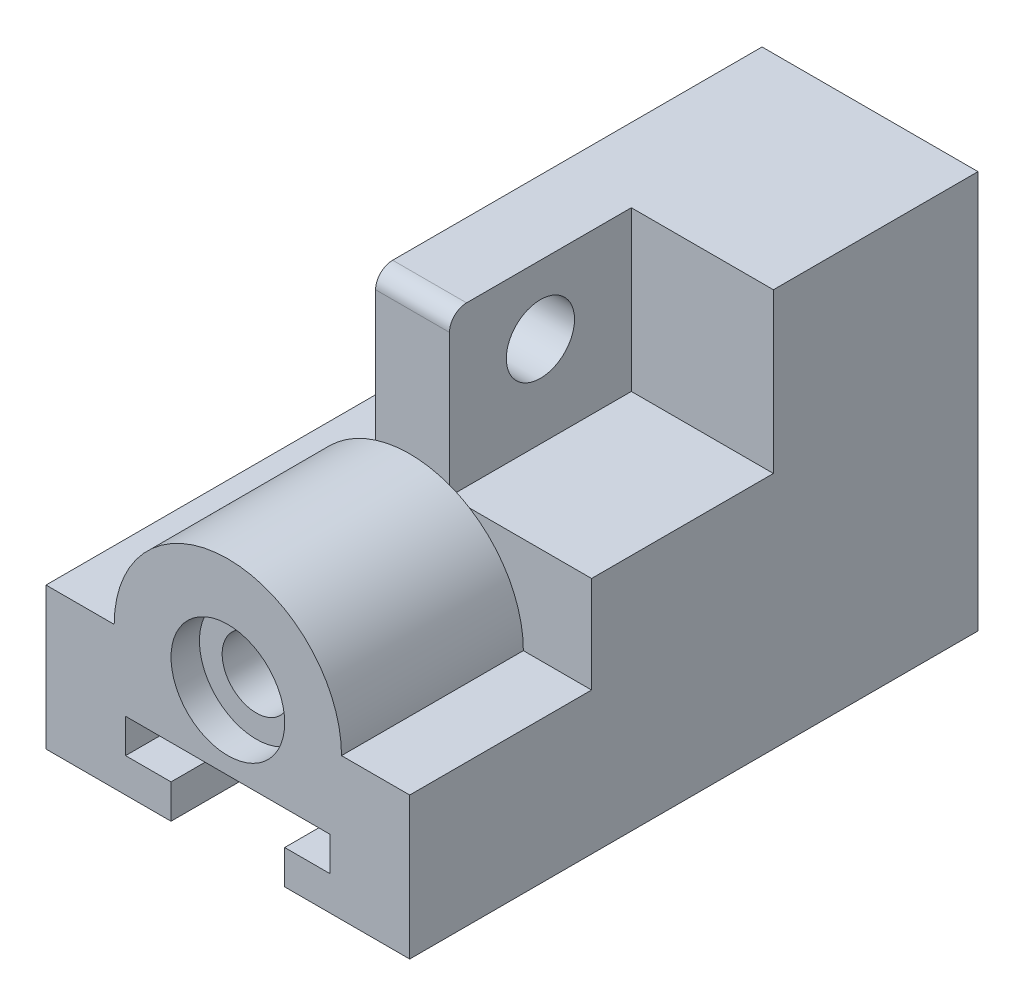
SolidWorks part; units mm, degrees
ref_plane "Front Plane" through (0, 0, 0) normal (0, 0, 1) x (1, 0, 0)
ref_plane "Top Plane" through (0, 0, 0) normal (0, 1, 0) x (1, 0, 0)
ref_plane "Right Plane" through (0, 0, 0) normal (1, 0, 0) x (0, 0, -1)
sketch "Sketch1" plane through (0, 0, 0) normal (0, 1, 0) x (1, 0, 0)
  line L1 (0, 0) -> (64, 0)
  line L2 (0, 0) -> (0, 100)
  line L3 (0, 100) -> (64, 100)
  line L4 (64, 0) -> (64, 100)
  dimension "D1" = 100
  dimension "D2" = 64
extrude "Boss-Extrude1" add sketch "Sketch1" against normal blind 25
sketch "Sketch2" plane through (0, 0, 0) normal (0, 1, 0) x (1, 0, 0)
  line L1 (64, 100) -> (26, 100)
  line L2 (64, 100) -> (64, 32)
  line L3 (64, 32) -> (26, 32)
  line L4 (26, 100) -> (26, 32)
  dimension "D1" = 38
  dimension "D2" = 68
extrude "Boss-Extrude2" add sketch "Sketch2" along normal blind 45
sketch "Sketch3" plane through (64, 0, 0) normal (1, 0, 0) x (0, 0, -1)
  line L1 (32, 45) -> (64, 45)
  line L2 (32, 45) -> (32, 17)
  line L3 (32, 17) -> (64, 17)
  line L4 (64, 45) -> (64, 17)
  dimension "D1" = 28
  dimension "D2" = 32
extrude "Cut-Extrude1" cut sketch "Sketch3" against normal blind 25
sketch "Sketch4" plane through (0, 0, 0) normal (0, 0, 1) x (1, 0, 0)
  line L0 (0, 0) -> (64, 0) construction
  line L1 (0, -25) -> (64, -25) construction
  line L2 (22, -25) -> (42, -25)
  line L3 (22, -25) -> (22, -19)
  line L5 (42, -25) -> (42, -19)
  line L6 (12, 0) -> (52, 0)
  line L7 (42, -19) -> (50, -19)
  line L8 (14, -13) -> (50, -13)
  line L9 (14, -13) -> (14, -19)
  line L10 (14, -19) -> (22, -19)
  line L11 (50, -13) -> (50, -19)
  arc A0 (52, 0) -> (12, 0) centre (32, 0) ccw
  point P15 (32, -13)
  point P16 (32, -25)
  point P17 (32, 20)
  line M11 (64, 0) -> (0, 0)
  line M13 (0, -25) -> (64, -25)
  dimension "D1" = 40
  dimension "D2" = 20
  dimension "D3" = 36
  dimension "D4" = 6
  dimension "D5" = 6
extrude "Boss-Extrude3" add sketch "Sketch4" against normal up to surface (32 mm away) contours A0 M11 region at (32, 8.4883, 0) up to face at (43, 20.6667, -32)
extrude "Cut-Extrude2" cut sketch "Sketch4<3>" against normal through all contours L11 L8 L9 L10 L3 L5 L7 M13 region at (32, -18.1429, 0)
sketch "Sketch4<3>" plane through (0, 0, 0) normal (0, 0, 1) x (1, 0, 0) same geometry as "Sketch4"
fillet "Fillet1" radius 3 1 edges at (32.5, 45, -32)
hole_wizard "CBORE for M10 Cheese Head Screw1" positions "Sketch6" profile "Sketch5" counterbore size "M10" standard "AS"
sketch "Sketch6" plane through (0, 0, 0) normal (0, 0, 1) x (1, 0, 0)
  arc A0 (52, 0) -> (12, 0) centre (32, 0) ccw construction
  point P0 (32, 0)
sketch "Sketch5" plane through (32, 0, 0) normal (1, 0, 0) x (0, -1, 0)
  line L0 (0, 0) -> (0, 25)
  line L1 (0, 25) -> (6, 25)
  line L2 (6, 25) -> (6, 5)
  line L3 (6, 5) -> (10, 5)
  line L4 (10, 5) -> (10, 0)
  line L5 (10, 0) -> (0, 0)
  line L10 (0, 25) -> (-6, 25) construction
  line L11 (0, -6.35) -> (0, 107.95) construction
  dimension "Hole Dia." = 12
  dimension "Hole Depth" = 25
  dimension "C'Bore Dia." = 20
  dimension "C'Bore Depth" = 5
  dimension "Drill Angle" = 180
sketch "Sketch7" plane through (39, 0, 0) normal (1, 0, 0) x (0, 0, -1)
  line L0 (32, 42) -> (32, 18.735) construction
  line L1 (64, 45) -> (35, 45) construction
  circle A0 centre (48, 33) radius 6
  dimension "D3" = 12
  dimension "D1" = 16
  dimension "D2" = 12
extrude "Cut-Extrude3" cut sketch "Sketch7" against normal through all
cosmetic thread "Cosmetic Thread1" parameters "D2"=12
cosmetic thread "Cosmetic Thread2" parameters "D1"=5, "D2"=14
